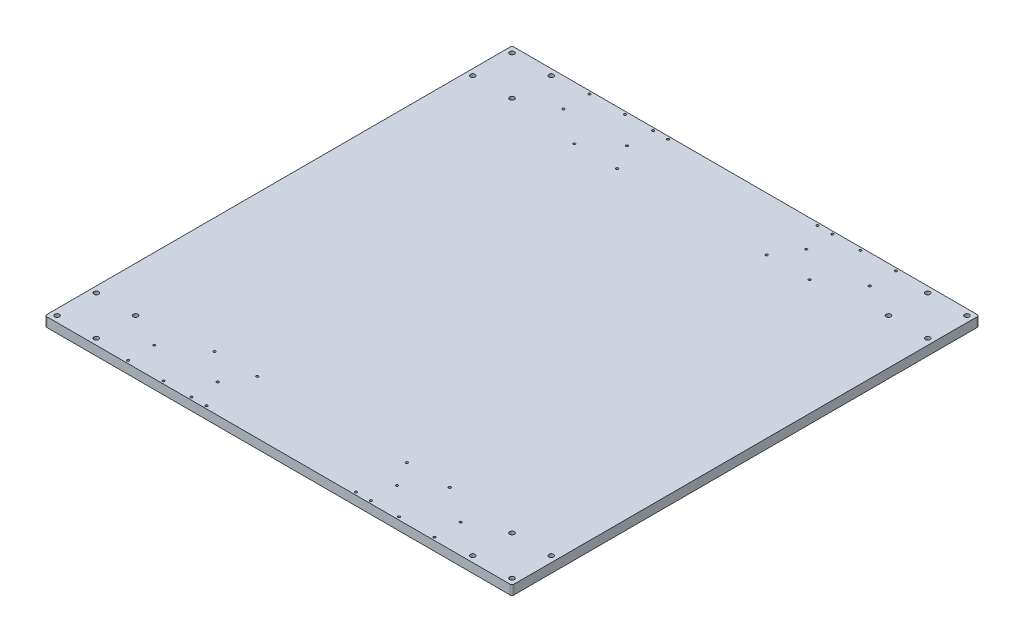
SolidWorks part; units mm, degrees
material "AISI 1045 Steel, cold drawn"
ref_plane "Front Plane" through (0, 0, 0) normal (0, 0, 1) x (1, 0, 0)
ref_plane "Top Plane" through (0, 0, 0) normal (0, 1, 0) x (1, 0, 0)
ref_plane "Right Plane" through (0, 0, 0) normal (1, 0, 0) x (0, 0, -1)
sketch "Sketch1" plane through (0, 0, 0) normal (0, 1, 0) x (1, 0, 0)
  line L1 (250, -250) -> (-250, -250)
  line L2 (250, -250) -> (250, 250)
  line L3 (250, 250) -> (-250, 250)
  line L4 (-250, -250) -> (-250, 250)
  line L5 (250, -250) -> (-250, 250) construction
  line L6 (250, 250) -> (-250, -250) construction
  point P0 (0, 0)
  dimension "D1" = 500
extrude "Boss-Extrude1" add sketch "Sketch1" along normal blind 10
sketch "Sketch2" plane through (0, 10, 0) normal (0, 1, 0) x (1, 0, 0)
  line L0 (250, -250) -> (250, 250) construction
  line L1 (164, -247) -> (96, -247)
  line L2 (164, -247) -> (164, -219)
  line L3 (164, -219) -> (96, -219)
  line L4 (96, -247) -> (96, -219)
  line L5 (-250, -250) -> (250, -250) construction
  line L6 (0, -1000) -> (0, 49000) construction
  line L7 (-96, -247) -> (-96, -219)
  line L8 (-164, -219) -> (-96, -219)
  line L9 (-164, -247) -> (-164, -219)
  line L10 (-164, -247) -> (-96, -247)
  line L11 (-1000, 0) -> (49000, 0) construction
  line L12 (-164, 247) -> (-96, 247)
  line L13 (-164, 247) -> (-164, 219)
  line L14 (-164, 219) -> (-96, 219)
  line L15 (-96, 247) -> (-96, 219)
  line L16 (96, 247) -> (96, 219)
  line L17 (164, 219) -> (96, 219)
  line L18 (164, 247) -> (164, 219)
  line L19 (164, 247) -> (96, 247)
  line L20 (-126, -192.6) -> (-80, -192.6)
  line L21 (126, -247) -> (80, -247)
  line L22 (126, -247) -> (126, -192.6)
  line L23 (126, -192.6) -> (80, -192.6)
  line L24 (80, -247) -> (80, -192.6)
  line L25 (-80, -247) -> (-80, -192.6)
  line L26 (-126, -247) -> (-80, -247)
  line L27 (-126, -247) -> (-126, -192.6)
  line L28 (126, 192.6) -> (80, 192.6)
  line L29 (80, 247) -> (80, 192.6)
  line L30 (126, 247) -> (80, 247)
  line L31 (126, 247) -> (126, 192.6)
  line L32 (-126, 247) -> (-126, 192.6)
  line L33 (-126, 247) -> (-80, 247)
  line L34 (-80, 247) -> (-80, 192.6)
  line L35 (-126, 192.6) -> (-80, 192.6)
  dimension "D1" = 86
  dimension "D2" = 68
  dimension "D3" = 28
  dimension "D4" = 3
  dimension "D5" = 30
  dimension "D6" = 46
  dimension "D7" = 54.4
hole_wizard "Tap Drill for M3x0.5 Tap1" positions "Sketch3" profile "Sketch4" hole size "M3x0.5" standard "ANSI Metric" end condition through all
sketch "Sketch3" plane through (0, 10, 0) normal (0, 1, 0) x (1, 0, 0)
  point P0 (164, -219)
  point P3 (164, -247)
  point P6 (96, -247)
  point P9 (96, -219)
  point P12 (-96, -219)
  point P15 (-164, -219)
  point P18 (-164, -247)
  point P21 (-96, -247)
  point P24 (-96, 219)
  point P27 (-96, 247)
  point P30 (-164, 247)
  point P33 (-164, 219)
  point P36 (96, 247)
  point P39 (164, 247)
  point P42 (164, 219)
  point P45 (96, 219)
  point P48 (-126, 247)
  point P51 (-80, 247)
  point P54 (-80, 192.6)
  point P56 (-126, 192.6)
  point P62 (80, 247)
  point P65 (126, 247)
  point P68 (126, 192.6)
  point P71 (80, 192.6)
  point P74 (80, -192.6)
  point P77 (126, -192.6)
  point P80 (126, -247)
  point P83 (80, -247)
  point P86 (-126, -192.6)
  point P89 (-80, -192.6)
  point P92 (-80, -247)
  point P95 (-126, -247)
sketch "Sketch4" plane through (164, 10, 219) normal (1, 0, 0) x (0, 0, 1)
  line L0 (0, 0) -> (0, 10)
  line L1 (0, 10) -> (1.25, 10)
  line L2 (1.25, 10) -> (1.25, 0)
  line L5 (1.25, 0) -> (0, 0)
  line L11 (0, -6.35) -> (0, 107.95) construction
  dimension "Thru Hole Dia." = 2.5
  dimension "Thru Hole Depth" = 10
hole_wizard "Tap Drill for M6x1.0 Tap1" positions "Sketch5" profile "Sketch6" hole size "M6x1.0" standard "ANSI Metric" end condition through all
sketch "Sketch5" plane through (0, 10, 0) normal (0, 1, 0) x (1, 0, 0)
  line L1 (243.5, -243.5) -> (201.5, -243.5)
  line L2 (243.5, -243.5) -> (243.5, -201.5)
  line L3 (243.5, -201.5) -> (201.5, -201.5)
  line L4 (201.5, -243.5) -> (201.5, -201.5)
  line L5 (201.5, -243.5) -> (243.5, -201.5) construction
  line L7 (250, -250) -> (250, 250) construction
  line L8 (-250, -250) -> (250, -250) construction
  circle A0 centre (222.5, -222.5) radius 27.5
  point P1 (243.5, -243.5)
  point P2 (201.5, -201.5)
  point P39 (243.5, -201.5)
  point P40 (201.5, -243.5)
  dimension "D3" = 55
  dimension "D1" = 42
  dimension "D2" = 42
sketch "Sketch6" plane through (243.5, 10, 243.5) normal (1, 0, 0) x (0, 0, 1)
  line L0 (0, 0) -> (0, 10)
  line L1 (0, 10) -> (2.5, 10)
  line L2 (2.5, 10) -> (2.5, 0)
  line L5 (2.5, 0) -> (0, 0)
  line L11 (0, -6.35) -> (0, 107.95) construction
  dimension "Thru Hole Dia." = 5
  dimension "Thru Hole Depth" = 10
ref_axis "Axis1" through (0, 10.5, 0) along (0, -1, 0)
pattern_circular "CirPattern1" count 4 over 360 about axis through (0, 10.5, 0) along (0, -1, 0) of "Tap Drill for M6x1.0 Tap1"
fillet "Fillet1" radius 2 4 edges at (250, 5, -250) (250, 5, 250) (-250, 5, 250) (-250, 5, -250)
